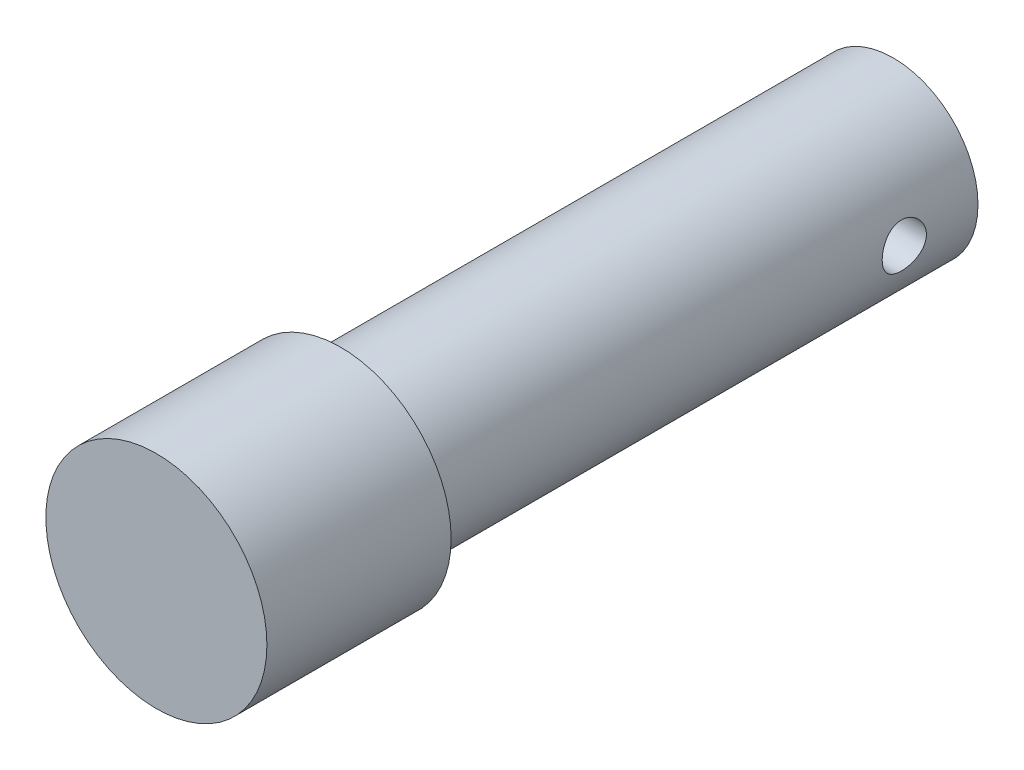
SolidWorks part; units mm, degrees
ref_plane "Front Plane" through (0, 0, 0) normal (0, 0, 1) x (1, 0, 0)
ref_plane "Top Plane" through (0, 0, 0) normal (0, 1, 0) x (1, 0, 0)
ref_plane "Right Plane" through (0, 0, 0) normal (1, 0, 0) x (0, 0, -1)
sketch "Sketch1" plane through (0, 0, 0) normal (0, 0, 1) x (1, 0, 0)
  circle A0 centre (0, 0) radius 2.3
  dimension "D1" = 4.6
extrude "Boss-Extrude1" add sketch "Sketch1" along normal blind 20
sketch "Sketch2" plane through (0, 0, 20) normal (0, 0, 1) x (1, 0, 0)
  circle A0 centre (0, 0) radius 3
  dimension "D1" = 6
extrude "Boss-Extrude2" add sketch "Sketch2" against normal blind 5
sketch "Sketch3" plane through (0, 0, 0) normal (1, 0, 0) x (0, 0, -1)
  line L0 (0, 0) -> (-2, 0) construction
  circle A0 centre (-2, 0) radius 0.6
  dimension "D2" = 1.2
  dimension "D1" = 2
extrude "Cut-Extrude1" cut sketch "Sketch3" against normal blind 5 and the other way blind 5
